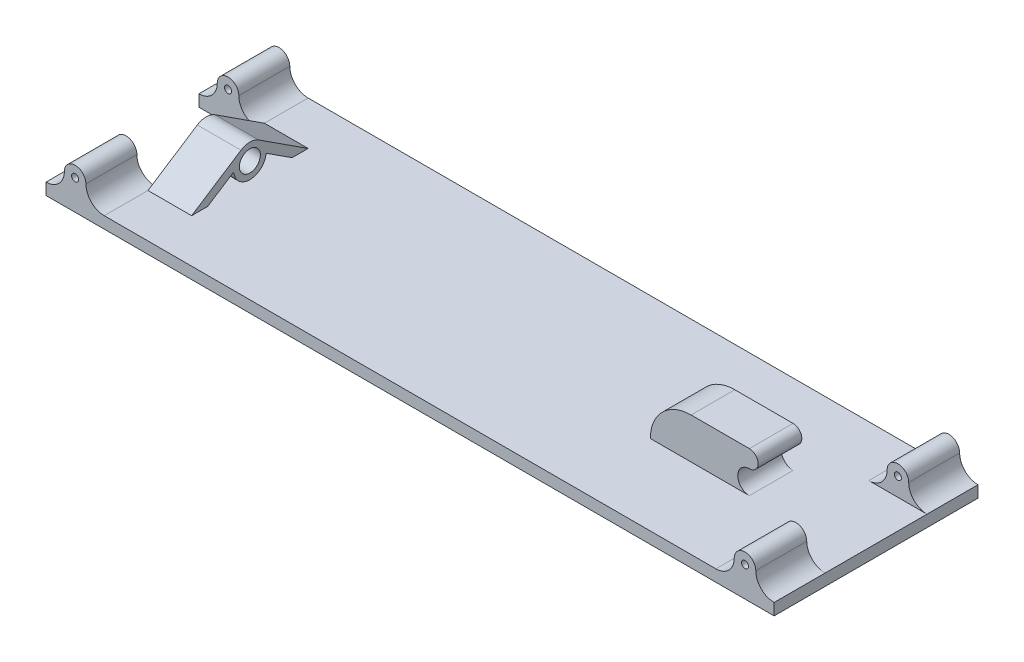
SolidWorks part; units mm, degrees
ref_plane "Front Plane" through (0, 0, 0) normal (0, 0, 1) x (1, 0, 0)
ref_plane "Top Plane" through (0, 0, 0) normal (0, 1, 0) x (1, 0, 0)
ref_plane "Right Plane" through (0, 0, 0) normal (1, 0, 0) x (0, 0, -1)
sketch "Sketch1" plane through (0, 0, 0) normal (0, 0, 1) x (1, 0, 0)
  line L1 (0, 0) -> (250, 0)
  line L2 (0, 0) -> (0, 4)
  line L3 (20, 4) -> (230, 4)
  line L4 (250, 0) -> (250, 4)
  circle A0 centre (10, 10.3) radius 1.2
  arc A1 (13.7, 10.3) -> (6.3, 10.3) centre (10, 10.3) ccw
  arc A2 (6.3, 10.3) -> (0, 4) centre (0, 10.3) cw
  arc A3 (13.7, 10.3) -> (20, 4) centre (20, 10.3) ccw
  circle A4 centre (240, 10.3) radius 1.2
  arc A5 (243.7, 10.3) -> (236.3, 10.3) centre (240, 10.3) ccw
  arc A6 (236.3, 10.3) -> (230, 4) centre (230, 10.3) cw
  arc A7 (243.7, 10.3) -> (250, 4) centre (250, 10.3) ccw
  point P13 (30, 5)
  point P20 (-8.8909, 16.0248)
  point P21 (0, 0)
  dimension "D3" = 2.4
  dimension "D4" = 2.5
  dimension "D5" = 20
  dimension "D1" = 4
  dimension "D2" = 250
extrude "Boss-Extrude1" add sketch "Sketch1" along normal mid plane 70
sketch "Sketch2" plane through (0, 0, 0) normal (1, 0, 0) x (0, 0, -1)
  line L0 (35, 14) -> (-35, 14) construction
  line L1 (17.5, 4) -> (-17.5, 4)
  line L2 (17.5, 4) -> (17.5, 14)
  line L3 (17.5, 14) -> (-17.5, 14)
  line L4 (-17.5, 4) -> (-17.5, 14)
  line L5 (17.5, 4) -> (-17.5, 14) construction
  line L6 (17.5, 14) -> (-17.5, 4) construction
  line L7 (-35, 4) -> (35, 4) construction
  point P0 (0, 9)
  point P9 (0, 0)
  dimension "D1" = 35
extrude "Cut-Extrude1" cut sketch "Sketch2" along normal through all
sketch "Sketch3" plane through (0, 0, 0) normal (0, 0, 1) x (1, 0, 0)
  line L0 (230, 4) -> (20, 4) construction
  line L1 (214, 18) -> (194, 18)
  line L2 (214, 4) -> (180, 4)
  arc A0 (214, 4) -> (214, 12) centre (214, 8) cw
  arc A1 (214, 12) -> (214, 18) centre (214, 15) ccw
  arc A2 (194, 18) -> (180, 4) centre (194, 4) ccw
  point P10 (0, 0)
  point P11 (0, 0)
  point P12 (178.2799, 4)
  point P14 (223.863, 11.9931)
  point P15 (222.5111, 16.5111)
  dimension "D1" = 3
  dimension "D2" = 4
  dimension "D3" = 20
  dimension "D4" = 180
extrude "Boss-Extrude2" add sketch "Sketch3" along normal mid plane 15
sketch "Sketch4" plane through (0, 4, 0) normal (0, 1, 0) x (1, 0, 0)
  line L0 (0, -17.5) -> (0, 17.5) construction
  line L1 (20, -17.5) -> (0, -17.5)
  line L2 (20, -17.5) -> (20, 17.5)
  line L3 (20, 17.5) -> (0, 17.5)
  line L4 (0, -17.5) -> (0, 17.5)
  line L5 (20, -17.5) -> (0, 17.5) construction
  line L6 (20, 17.5) -> (0, -17.5) construction
  point P0 (10, 0)
  point P7 (0, 0)
  point P8 (0, 0)
  dimension "D1" = 20
  dimension "D2" = 35
extrude "Cut-Extrude2" cut sketch "Sketch4" against normal through all
sketch "Sketch6" plane through (0, 0, 0) normal (1, 0, 0) x (0, 0, -1)
  line L0 (0, -1000) -> (0, 49000) construction
  line L1 (-35, 0) -> (35, 0) construction
  line L2 (-14.4879, 4) -> (-5.576, 9.7817)
  line L3 (-3.0479, 14.9979) -> (-20, 4)
  line L4 (-20, 4) -> (-14.4879, 4)
  line L6 (-17.5, 4) -> (17.5, 4) construction
  line L7 (20, 4) -> (14.4879, 4)
  line L8 (3.0479, 14.9979) -> (20, 4)
  line L9 (14.4879, 4) -> (5.576, 9.7817)
  circle A0 centre (0, 10.3) radius 3.6
  arc A1 (3.0479, 14.9979) -> (-3.0479, 14.9979) centre (0, 10.3) ccw
  arc A2 (-5.576, 9.7817) -> (5.576, 9.7817) centre (0, 10.3) ccw
  point P5 (0, 0)
  point P6 (-3.9122, 19.7813)
  dimension "D1" = 3.6
  dimension "D2" = 2
  dimension "D3" = 3
  dimension "D4" = 10.3
  dimension "D5" = 20
extrude "Boss-Extrude3" add sketch "Sketch6" along normal blind 15 from offset 20
